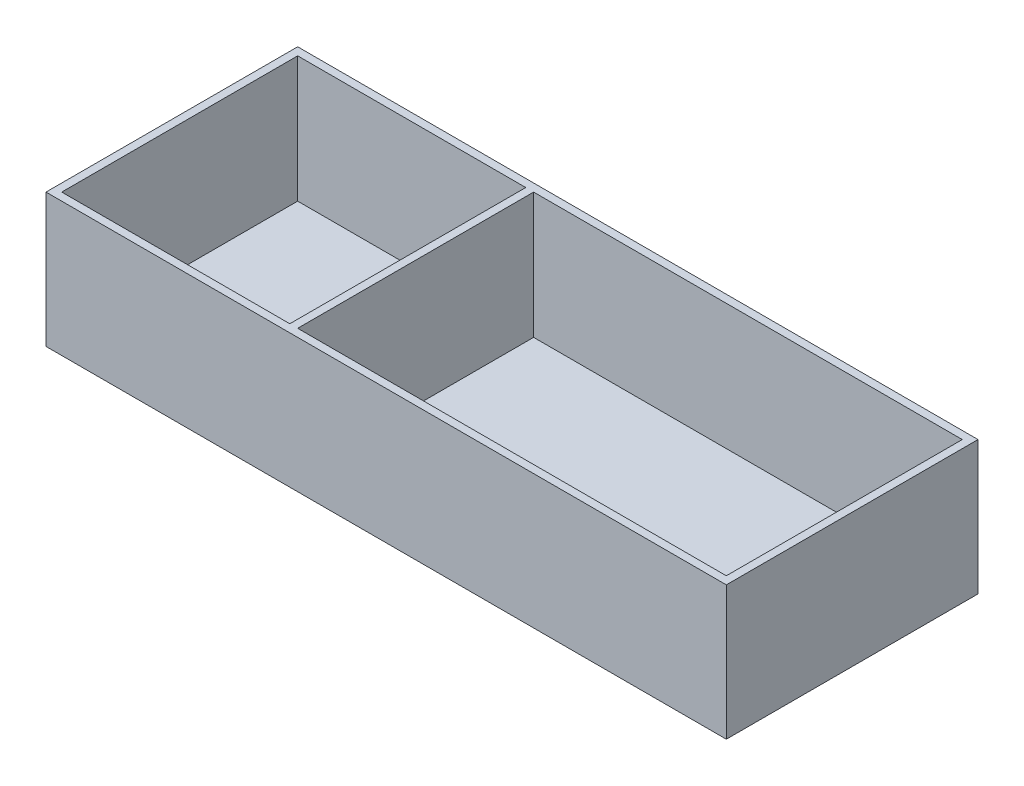
SolidWorks part; units mm, degrees
ref_plane "Front" through (0, 0, 0) normal (0, 0, 1) x (1, 0, 0)
ref_plane "Top" through (0, 0, 0) normal (0, 1, 0) x (1, 0, 0)
ref_plane "Right" through (0, 0, 0) normal (1, 0, 0) x (0, 0, -1)
sketch "Sketch1" plane through (0, 0, 0) normal (0, 1, 0) x (1, 0, 0)
  line L1 (-86.5, -32) -> (86.5, -32)
  line L2 (-86.5, -32) -> (-86.5, 32)
  line L3 (-86.5, 32) -> (86.5, 32)
  line L4 (86.5, -32) -> (86.5, 32)
  line L5 (-86.5, -32) -> (86.5, 32) construction
  line L6 (-86.5, 32) -> (86.5, -32) construction
  point P0 (0, 0)
  dimension "D1" = 64
  dimension "D2" = 173
extrude "Boss-Extrude1" add sketch "Sketch1" along normal blind 34
shell "Shell1" thickness 2 removed face at (0, 34, 0)
sketch "Sketch3" plane through (0, 2, 0) normal (0, 1, 0) x (1, 0, 0)
  line L0 (84.5, 30) -> (-84.5, 30) construction
  line L1 (-26.5, -30) -> (-24.5, -30)
  line L2 (-26.5, -30) -> (-26.5, 30)
  line L3 (-26.5, 30) -> (-24.5, 30)
  line L4 (-24.5, -30) -> (-24.5, 30)
  line L5 (-26.5, -30) -> (-24.5, 30) construction
  line L6 (-26.5, 30) -> (-24.5, -30) construction
  line L8 (84.5, -30) -> (84.5, 30) construction
  point P0 (-25.5, 0)
  dimension "D1" = 2
  dimension "D2" = 109
extrude "Boss-Extrude2" add sketch "Sketch3" along normal up to vertex (32 mm away) up to point (84.5, 34, -30)
